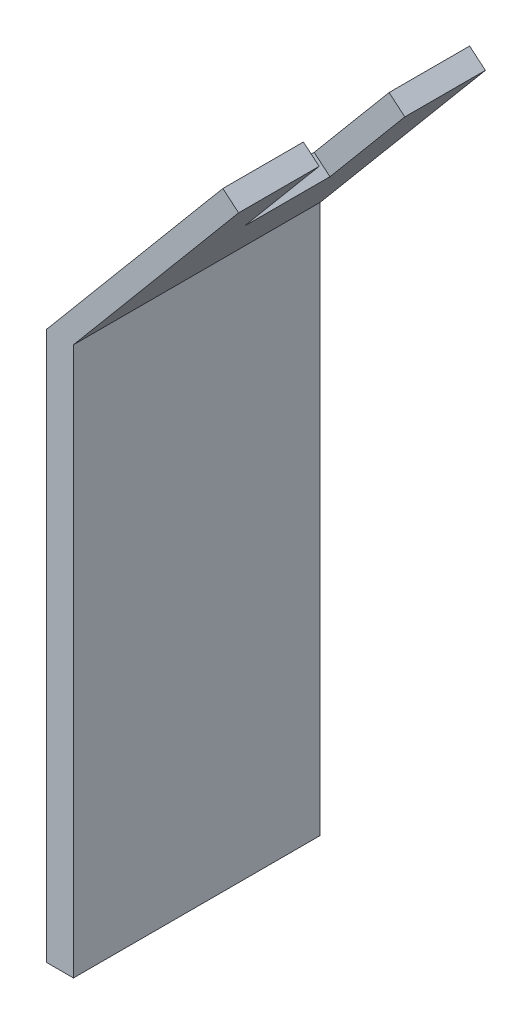
SolidWorks part; units mm, degrees
ref_plane "Plan de face" through (0, 0, 0) normal (0, 0, 1) x (1, 0, 0)
ref_plane "Plan de dessus" through (0, 0, 0) normal (0, 1, 0) x (1, 0, 0)
ref_plane "Plan de droite" through (0, 0, 0) normal (1, 0, 0) x (0, 0, -1)
sketch "Esquisse1" plane through (0, 0, 0) normal (0, 0, 1) x (1, 0, 0)
  line L0 (0, 0) -> (0, 80)
  line L1 (0, 80) -> (25.7115, 110.6418)
  line L2 (25.7115, 110.6418) -> (28.0096, 108.7134)
  line L3 (28.0096, 108.7134) -> (3.9162, 80)
  line L4 (3.9162, 80) -> (3.9162, 0)
  line L5 (3.9162, 0) -> (0, 0)
  line L6 (0, 80) -> (50000, 80) construction
  dimension "D1" = 80
  dimension "D2" = 40
  dimension "D3" = 3
  dimension "D4" = 50
extrude "Boss.-Extru.1" add sketch "Esquisse1" along normal blind 18 and the other way blind 18
sketch "Esquisse2" plane through (-39.3923, 33.0541, 0) normal (-0.766, 0.6428, 0) x (0, 0, 1)
  line L0 (-6.25, 101.2836) -> (-6.25, 84.2836)
  line L1 (-18, 101.2836) -> (18, 101.2836) construction
  line L2 (-6.25, 84.2836) -> (6.25, 84.2836)
  line L3 (6.25, 84.2836) -> (6.25, 101.2836)
  line L4 (0, 115.1754) -> (0, 50115.1754) construction
  line L5 (-6.25, 101.2836) -> (6.25, 101.2836)
  point P8 (0, 101.2836)
  dimension "D1" = 17
  dimension "D2" = 12.5
extrude "Enlèv. mat.-Extru.1" cut sketch "Esquisse2" against normal up to surface (3 mm away) up to face at (15.9629, 94.3567, 0)
